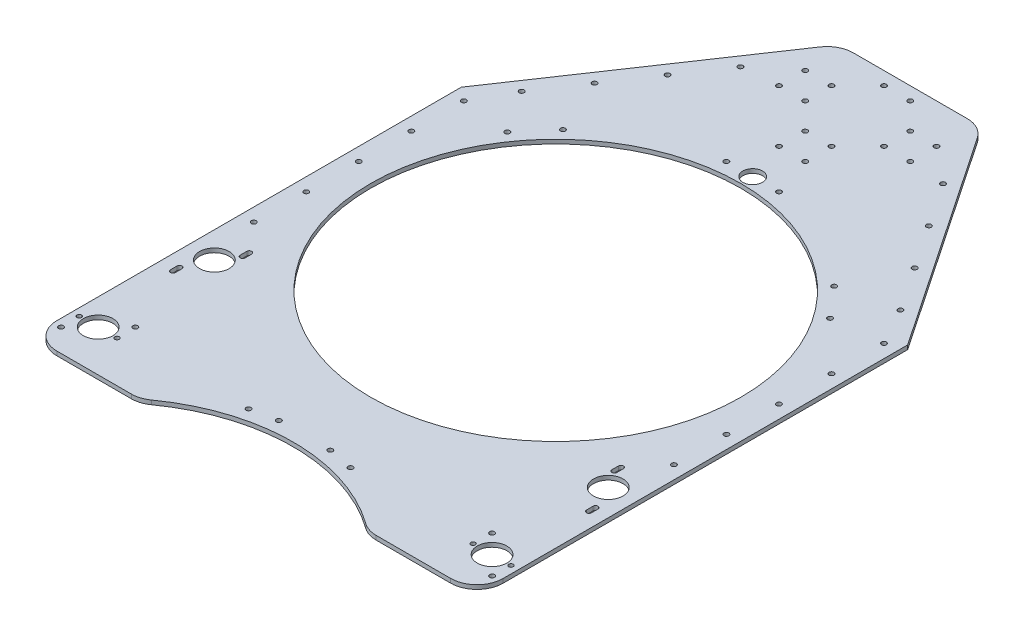
SolidWorks part; units mm, degrees
material "Thornel Mat VMA"
ref_plane "Front Plane" through (0, 0, 0) normal (0, 0, 1) x (1, 0, 0)
ref_plane "Top Plane" through (0, 0, 0) normal (0, 1, 0) x (1, 0, 0)
ref_plane "Right Plane" through (0, 0, 0) normal (1, 0, 0) x (0, 0, -1)
sketch "Sketch1" plane through (0, 0, 0) normal (0, 1, 0) x (1, 0, 0)
  line L1 (-215.9, 342.9) -> (215.9, 342.9)
  line L2 (-215.9, 342.9) -> (-215.9, -342.9)
  line L3 (-215.9, -342.9) -> (215.9, -342.9)
  line L4 (215.9, 342.9) -> (215.9, -342.9)
  line L5 (-215.9, 342.9) -> (215.9, -342.9) construction
  line L6 (-215.9, -342.9) -> (215.9, 342.9) construction
  point P0 (0, 0)
  dimension "D1" = 431.8
  dimension "D2" = 685.8
extrude "Boss-Extrude1" add sketch "Sketch1" along normal blind 4
sketch "Sketch2" plane through (0, 4, 0) normal (0, 1, 0) x (1, 0, 0)
  line L0 (0, -342.9) -> (0, 342.9) construction
  line L1 (-215.9, -342.9) -> (215.9, -342.9) construction
  line L2 (215.9, 342.9) -> (-215.9, 342.9) construction
  line L3 (-215.9, 342.9) -> (-215.9, -342.9) construction
  line L4 (-208.4605, -320.8555) -> (-190.5, -302.895) construction
  line L5 (-193.1461, -302.895) -> (-215.9, -302.895) construction
  line L6 (190.5, -215.9) -> (190.5, -165.1) construction
  line L7 (190.5, -190.5) -> (201.2345, -213.5202) construction
  line L8 (201.2345, -213.5202) -> (179.7655, -167.4798) construction
  line L9 (-208.4605, -320.8555) -> (-172.5395, -284.9345) construction
  line L10 (203.6158, -219.8702) -> (203.6158, -213.5202)
  line L11 (198.8533, -219.8702) -> (198.8533, -213.5202)
  line L12 (182.1467, -173.8298) -> (182.1467, -167.4798)
  line L13 (177.3842, -173.8298) -> (177.3842, -167.4798)
  line L14 (-198.8533, -219.8702) -> (-198.8533, -213.5202)
  line L15 (-203.6158, -219.8702) -> (-203.6158, -213.5202)
  line L16 (-177.3842, -173.8298) -> (-177.3842, -167.4798)
  line L17 (-182.1467, -173.8298) -> (-182.1467, -167.4798)
  circle A0 centre (-190.5, -302.895) radius 14.3129
  circle A1 centre (-190.5, -190.5) radius 14.3129
  circle A3 centre (190.5, -190.5) radius 14.3129
  circle A4 centre (190.5, -190.5) radius 25.4 construction
  circle A5 centre (-190.5, -190.5) radius 25.4 construction
  circle A6 centre (201.2345, -213.5202) radius 2.3812
  circle A7 centre (179.7655, -167.4798) radius 2.3813
  circle A10 centre (-190.5, -302.895) radius 25.4 construction
  circle A11 centre (-208.4605, -320.8555) radius 2.3813
  circle A15 centre (-172.5395, -284.9345) radius 2.3813
  circle A16 centre (172.5395, -284.9345) radius 2.3813
  circle A17 centre (208.4605, -320.8555) radius 2.3813
  circle A18 centre (190.5, -302.895) radius 14.3129
  circle A19 centre (-179.7655, -167.4798) radius 2.3813
  circle A20 centre (-201.2345, -213.5202) radius 2.3813
  circle A21 centre (208.788, -302.895) radius 2.159
  circle A22 centre (172.212, -302.895) radius 2.159
  circle A23 centre (-172.212, -302.895) radius 2.159
  circle A24 centre (-208.788, -302.895) radius 2.159
  circle A25 centre (179.7655, -173.8298) radius 2.3813
  circle A26 centre (201.2345, -219.8702) radius 2.3813
  circle A27 centre (-201.2345, -219.8702) radius 2.3813
  circle A28 centre (-179.7655, -173.8298) radius 2.3813
  point P33 (-190.5, -304.8)
  point P34 (-189.5475, -303.8475)
  point P48 (190.5, -302.895)
  dimension "D1" = 28.6258
  dimension "D2" = 28.6258
  dimension "D6" = 50.8
  dimension "D7" = 50.8
  dimension "D8" = 4.7625
  dimension "D9" = 4.7625
  dimension "D10" = 18.288
  dimension "D11" = 4.318
  dimension "D12" = 50.8
  dimension "D13" = 4.7625
  dimension "D18" = 4.7625
  dimension "D20" = 4.7625
  dimension "D3" = 40.005
  dimension "D4" = 112.395
  dimension "D5" = 25.4
  dimension "D15" = 45
  dimension "D16" = 25
  dimension "D19" = 6.35
  dimension "D21" = 6.35
  dimension "D14" = 2
  dimension "D17" = 2
extrude "Cut-Extrude1" cut sketch "Sketch2" against normal through all contours A18 | A17 | A21 | A22 | A16 | A26 | A26 L10 A6 L11 | A6 | A3 | A25 | A25 L12 A7 L13 | A7 | A19 | A28 | L17 A28 L16 A19 | A1 | A20 | A27 | A0 | A11 | A24 | A23 | A15 | L15 A27 L14 A20 region at (201.2345, 4, 216.6952) region at (201.2345, 4, 219.8702) region at (201.2345, 4, 213.5202) region at (179.7655, 4, 170.6548) region at (179.7655, 4, 173.8298) region at (179.7655, 4, 167.4798) region at (-201.2345, 4, 216.6952) region at (-201.2345, 4, 219.8702) region at (-201.2345, 4, 213.5202) region at (-179.7655, 4, 170.6548) region at (-179.7655, 4, 173.8298) region at (-179.7655, 4, 167.4798) region at (-190.5, 4, 302.895) region at (-190.5, 4, 190.5) region at (190.5, 4, 190.5) region at (-208.4605, 4, 320.8555) region at (-172.5395, 4, 284.9345) region at (172.5395, 4, 284.9345) region at (208.4605, 4, 320.8555) region at (190.5, 4, 302.895) region at (208.788, 4, 302.895) region at (172.212, 4, 302.895) region at (-172.212, 4, 302.895) region at (-208.788, 4, 302.895)
sketch "Sketch3" plane through (0, 0, 0) normal (0, -1, 0) x (-1, 0, 0)
  line L1 (29.8706, 270.2084) -> (-24.7394, 270.2084)
  line L2 (29.8706, 270.2084) -> (29.8706, 216.2334)
  line L3 (29.8706, 216.2334) -> (-24.7394, 216.2334)
  line L4 (-24.7394, 270.2084) -> (-24.7394, 216.2334)
  line L5 (29.8706, 270.2084) -> (-24.7394, 216.2334) construction
  line L6 (29.8706, 216.2334) -> (-24.7394, 270.2084) construction
  point P0 (2.5656, 243.2209)
  dimension "D1" = 53.975
  dimension "D2" = 54.61
extrude "Boss-Extrude2" [suppressed] add sketch "Sketch3" along normal blind 203.2
fillet "Fillet1" [suppressed] radius 20.32
sketch "Sketch4" [suppressed] plane through (0, -203.2, 0) normal (0, -1, 0) x (-1, 0, 0)
  line L0 (-24.7394, 216.2334) -> (29.8706, 216.2334) construction
  line L1 (26.6956, 267.0334) -> (-21.5644, 267.0334)
  line L2 (26.6956, 267.0334) -> (26.6956, 219.4084)
  line L3 (26.6956, 219.4084) -> (-21.5644, 219.4084)
  line L4 (-21.5644, 267.0334) -> (-21.5644, 219.4084)
  line L5 (26.6956, 267.0334) -> (-21.5644, 219.4084) construction
  line L6 (26.6956, 219.4084) -> (-21.5644, 267.0334) construction
  line L7 (29.8706, 270.2084) -> (-24.7394, 270.2084) construction
  line L8 (29.8706, 216.2334) -> (29.8706, 270.2084) construction
  line L9 (-24.7394, 270.2084) -> (-24.7394, 216.2334) construction
  point P0 (2.5656, 243.2209)
  dimension "D1" = 3.175
  dimension "D2" = 3.175
  dimension "D3" = 3.175
  dimension "D4" = 3.175
extrude "Cut-Extrude2" [suppressed] cut sketch "Sketch4" against normal blind 203.2
sketch "Sketch5" [suppressed] plane through (-29.8706, 0, 0) normal (-1, 0, 0) x (0, 0, 1)
  line L0 (-216.2334, -203.2) -> (-216.2334, 0) construction
  line L1 (-216.2334, -203.2) -> (-270.2084, -203.2) construction
  circle A0 centre (-243.2209, -184.15) radius 14.2875
  dimension "D1" = 28.575
  dimension "D2" = 26.9875
  dimension "D3" = 19.05
extrude "Cut-Extrude3" [suppressed] cut sketch "Sketch5" against normal blind 203.2
sketch "Sketch6" plane through (0, 4, 0) normal (0, 1, 0) x (1, 0, 0)
  circle A0 centre (0, -50.8) radius 179.07
  dimension "D1" = 358.14
  dimension "D2" = 50.8
extrude "Cut-Extrude4" cut sketch "Sketch6" against normal through all
sketch "Sketch8" plane through (0, 4, 0) normal (0, 1, 0) x (1, 0, 0)
  circle A0 centre (0, 139.7) radius 9.525
  circle A2 centre (0, 139.7) radius 25.4 construction
  circle A3 centre (25.4, 139.7) radius 2.3813
  circle A4 centre (-25.4, 139.7) radius 2.3813
  dimension "D1" = 19.05
  dimension "D3" = 50.8
  dimension "D4" = 4.7625
  dimension "D5" = 4.7625
  dimension "D2" = 139.7
extrude "Cut-Extrude6" cut sketch "Sketch8" against normal through all
fillet "Fillet2" radius 25.4 2 edges at (215.9, 2, 342.9) (-215.9, 2, 342.9)
sketch "Sketch10" plane through (0, 4, 0) normal (0, 1, 0) x (1, 0, 0)
  line L0 (-215.9, 342.9) -> (-215.9, -317.5) construction
  line L1 (215.9, -317.5) -> (215.9, 342.9) construction
  circle A0 centre (-190.5, 215.9) radius 14.3129
  circle A1 centre (190.5, 215.9) radius 14.3129
  circle A2 centre (-190.5, 215.9) radius 25.4 construction
  circle A3 centre (190.5, 215.9) radius 25.4 construction
  circle A4 centre (190.5, 190.5) radius 2.3813
  circle A5 centre (190.5, 241.3) radius 2.3813
  circle A6 centre (-190.5, 190.5) radius 2.3813
  circle A7 centre (-190.5, 241.3) radius 2.3813
  circle A8 centre (190.5, -190.5) radius 14.3129 construction
  circle A9 centre (-190.5, -190.5) radius 14.3129 construction
  dimension "D1" = 28.6258
  dimension "D2" = 50.8
  dimension "D3" = 28.6258
  dimension "D4" = 50.8
  dimension "D5" = 4.7625
  dimension "D6" = 4.7625
  dimension "D7" = 4.7625
  dimension "D8" = 4.7625
  dimension "D9" = 25.4
  dimension "D10" = 25.4
  dimension "D11" = 406.4
  dimension "D12" = 406.4
extrude "Cut-Extrude8" [suppressed] cut sketch "Sketch10" against normal through all
sketch "Sketch11" plane through (0, 4, 0) normal (0, 1, 0) x (1, 0, 0)
  line L0 (0, -50.8) -> (156.0485, 58.4663) construction
  line L6 (0, 0) -> (0, 139.7) construction
  circle A0 centre (0, -50.8) radius 179.07
  circle A1 centre (0, -50.8) radius 179.07 construction
  circle A2 centre (0, -50.8) radius 184.15
  circle A3 centre (0, -50.8) radius 215.9
  circle A4 centre (156.0485, 58.4663) radius 2.3813
  circle A5 centre (131.1838, 87.3342) radius 2.3813
  circle A6 centre (0, -50.8) radius 190.5 construction
  circle A7 centre (-131.1838, 87.3342) radius 2.3813
  circle A8 centre (-156.0485, 58.4663) radius 2.3813
  dimension "D1" = 368.3
  dimension "D6" = 431.8
  dimension "D7" = 381
  dimension "D9" = 4.7625
  dimension "D10" = 4.7625
  dimension "D2" = 55
  dimension "D8" = 38.1
extrude "Cut-Extrude9" cut sketch "Sketch11" against normal through all contours A4 | A5 | A7 | A8 region at (156.0485, 4, -58.4663) region at (131.1838, 4, -87.3342) region at (-131.1838, 4, -87.3342) region at (-156.0485, 4, -58.4663)
sketch "Sketch13" plane through (0, 4, 0) normal (0, 1, 0) x (1, 0, 0)
  line L0 (-215.9, 342.9) -> (-215.9, -317.5) construction
  line L1 (215.9, 342.9) -> (-215.9, 342.9) construction
  line L2 (0, -342.9) -> (0, 342.9) construction
  line L3 (-190.5, -342.9) -> (190.5, -342.9) construction
  circle A0 centre (-203.2, 317.5) radius 2.3813
  circle A1 centre (-203.2, 266.7) radius 2.3813
  circle A2 centre (-203.2, 215.9) radius 2.3813
  circle A3 centre (-203.2, 165.1) radius 2.3813
  circle A4 centre (-203.2, 114.3) radius 2.3813
  circle A5 centre (-203.2, 63.5) radius 2.3813
  circle A6 centre (-203.2, 12.7) radius 2.3813
  circle A7 centre (-203.2, -38.1) radius 2.3813
  circle A8 centre (-203.2, -88.9) radius 2.3813
  circle A9 centre (-203.2, -139.7) radius 2.3813
  circle A10 centre (203.2, -139.7) radius 2.3813
  circle A11 centre (203.2, 12.7) radius 2.3813
  circle A12 centre (203.2, 63.5) radius 2.3813
  circle A13 centre (203.2, 114.3) radius 2.3813
  circle A14 centre (203.2, 165.1) radius 2.3813
  circle A15 centre (203.2, 266.7) radius 2.3813
  circle A16 centre (203.2, 317.5) radius 2.3813
  circle A17 centre (-25.4, -330.2) radius 2.4664
  circle A20 centre (-50.8, -330.2) radius 2.3078
  circle A21 centre (50.8, -330.2) radius 2.3078
  circle A22 centre (25.4, -330.2) radius 2.4664
  circle A23 centre (203.2, -88.9) radius 2.3813
  circle A24 centre (203.2, -38.1) radius 2.3813
  circle A25 centre (203.2, 215.9) radius 2.3813
  dimension "D1" = 4.7625
  dimension "D2" = 12.7
  dimension "D3" = 25.4
  dimension "D5" = 25.4
  dimension "D6" = 50.8
  dimension "D7" = 12.7
  dimension "D8" = 12.7
  dimension "D4" = 10
extrude "Cut-Extrude10" cut sketch "Sketch13" against normal through all
sketch "Sketch14" plane through (0, 4, 0) normal (0, 1, 0) x (1, 0, 0)
  line L0 (215.9, -317.5) -> (215.9, 342.9) construction
  line L1 (0, -342.9) -> (0, -229.87) construction
  line L2 (-190.5, -342.9) -> (190.5, -342.9) construction
  circle A0 centre (209.55, -245.745) radius 2.3813
  circle A2 centre (0, -50.8) radius 179.07 construction
  circle A3 centre (-209.55, -245.745) radius 2.3813
  circle A4 centre (190.5, -302.895) radius 14.3129 construction
  dimension "D1" = 57.15
  dimension "D3" = 4.7625
  dimension "D2" = 6.35
extrude "Cut-Extrude11" [suppressed] cut sketch "Sketch14" against normal through all
sketch "Sketch16" plane through (0, 4, 0) normal (0, 1, 0) x (1, 0, 0)
  line L0 (215.9, -317.5) -> (215.9, 342.9) construction
  line L1 (-215.9, 342.9) -> (215.9, 342.9)
  line L2 (-215.9, 342.9) -> (-215.9, 292.1)
  line L3 (-215.9, 292.1) -> (215.9, 292.1)
  line L4 (215.9, 342.9) -> (215.9, 292.1)
  dimension "D1" = 50.8
extrude "Cut-Extrude13" cut sketch "Sketch16" against normal through all
sketch "Sketch17" plane through (0, 0, 0) normal (0, -1, 0) x (-1, 0, 0)
  line L0 (0, -482.6) -> (0, 3.1553) construction
  line L1 (0, -482.6) -> (24.8652, -293.7298) construction
  line L2 (0, -482.6) -> (49.305, -298.5911) construction
  circle A0 centre (0, -482.6) radius 177.8
  circle A1 centre (0, -482.6) radius 190.5 construction
  circle A2 centre (24.8652, -293.7298) radius 2.3813
  circle A3 centre (49.305, -298.5911) radius 2.3813
  circle A4 centre (-24.8652, -293.7298) radius 2.3813
  circle A5 centre (-49.305, -298.5911) radius 2.3813
  dimension "D1" = 355.6
  dimension "D3" = 381
  dimension "D6" = 4.7625
  dimension "D7" = 4.7625
  dimension "D2" = 482.6
  dimension "D4" = 7.5
  dimension "D5" = 15
extrude "Cut-Extrude14" cut sketch "Sketch17" against normal through all
fillet "Fillet3" radius 25.4 2 edges at (109.9852, 2, 342.9) (-109.9852, 2, 342.9)
sketch "Sketch18" plane through (0, 4, 0) normal (0, 1, 0) x (1, 0, 0)
  line L0 (-215.9, 292.1) -> (215.9, 292.1) construction
  line L1 (25.4, 215.9) -> (-25.4, 215.9) construction
  line L2 (25.4, 215.9) -> (25.4, 266.7) construction
  line L3 (25.4, 266.7) -> (-25.4, 266.7) construction
  line L4 (-25.4, 215.9) -> (-25.4, 266.7) construction
  line L5 (25.4, 215.9) -> (-25.4, 266.7) construction
  line L6 (25.4, 266.7) -> (-25.4, 215.9) construction
  line L8 (25.4, 215.9) -> (76.2, 215.9) construction
  line L9 (25.4, 215.9) -> (25.4, 266.7) construction
  line L10 (25.4, 266.7) -> (76.2, 266.7) construction
  line L11 (76.2, 215.9) -> (76.2, 266.7) construction
  circle A0 centre (38.1, 228.6) radius 2.3812
  circle A1 centre (63.5, 228.6) radius 2.3813
  circle A2 centre (63.5, 254) radius 2.3813
  circle A3 centre (38.1, 254) radius 2.3813
  circle A4 centre (-12.7, 177.8) radius 2.3813
  circle A5 centre (-12.7, 203.2) radius 2.3813
  circle A6 centre (12.7, 177.8) radius 2.3813
  circle A7 centre (12.7, 203.2) radius 2.3812
  circle A8 centre (-63.5, 254) radius 2.3812
  circle A9 centre (-38.1, 254) radius 2.3813
  circle A10 centre (-63.5, 228.6) radius 2.3813
  circle A11 centre (-38.1, 228.6) radius 2.3813
  circle A12 centre (12.7, 304.8) radius 2.3812
  circle A13 centre (12.7, 279.4) radius 2.3812
  circle A14 centre (-12.7, 304.8) radius 2.3813
  circle A15 centre (-12.7, 279.4) radius 2.3812
  point P0 (0, 241.3)
  point P45 (0, 241.3)
  dimension "D5" = 4.7625
  dimension "D1" = 50.8
  dimension "D2" = 50.8
  dimension "D3" = 50.8
  dimension "D4" = 12.7
  dimension "D6" = 25.4
  dimension "D9" = 50.8
  dimension "D10" = 4
  dimension "D7" = 2
  dimension "D8" = 2
extrude "Cut-Extrude15" cut sketch "Sketch18" against normal through all
chamfer "Chamfer1" distance 147.32 angle 56 1 edges at (215.9, 2, -292.1) first distance on face at (0, 2, -292.1)
chamfer "Chamfer2" distance 147.32 angle 56 1 edges at (-215.9, 2, -292.1) first distance on face at (-73.66, 2, -292.1)
fillet "Fillet4" radius 25.4 2 edges at (68.58, 2, -292.1) (-68.58, 2, -292.1)
sketch "Sketch19" plane through (0, 4, 0) normal (0, 1, 0) x (1, 0, 0)
  line L0 (-76.1321, 280.9035) -> (-215.9, 73.6891) construction
  line L1 (-55.0746, 292.1) -> (55.0746, 292.1) construction
  line L2 (0, 292.1) -> (0, -304.8) construction
  circle A0 centre (-97.9769, 225.806) radius 2.3813
  circle A2 centre (-126.3839, 183.6909) radius 2.3813
  circle A3 centre (-154.7909, 141.5758) radius 2.3813
  circle A4 centre (-183.1979, 99.4607) radius 2.3813
  arc A5 (103.6505, -338.1375) -> (-103.6505, -338.1375) centre (0, -482.6) ccw construction
  circle A6 centre (183.1979, 99.4607) radius 2.3813
  circle A7 centre (154.7909, 141.5758) radius 2.3813
  circle A8 centre (126.3839, 183.6909) radius 2.3812
  circle A9 centre (97.9769, 225.806) radius 2.3813
  dimension "D1" = 12.7
  dimension "D2" = 4.7625
  dimension "D3" = 66.294
  dimension "D4" = 4
extrude "Cut-Extrude16" cut sketch "Sketch19" against normal through all
sketch "Sketch20" plane through (0, 4, 0) normal (0, 1, 0) x (1, 0, 0)
  line L5 (251.0039, -358.5351) -> (-248.9961, -358.5351)
  line L6 (251.0039, -358.5351) -> (251.0039, 241.4649)
  line L7 (251.0039, 241.4649) -> (-248.9961, 241.4649)
  line L8 (-248.9961, -358.5351) -> (-248.9961, 241.4649)
  dimension "D1" = 600
  dimension "D2" = 500
